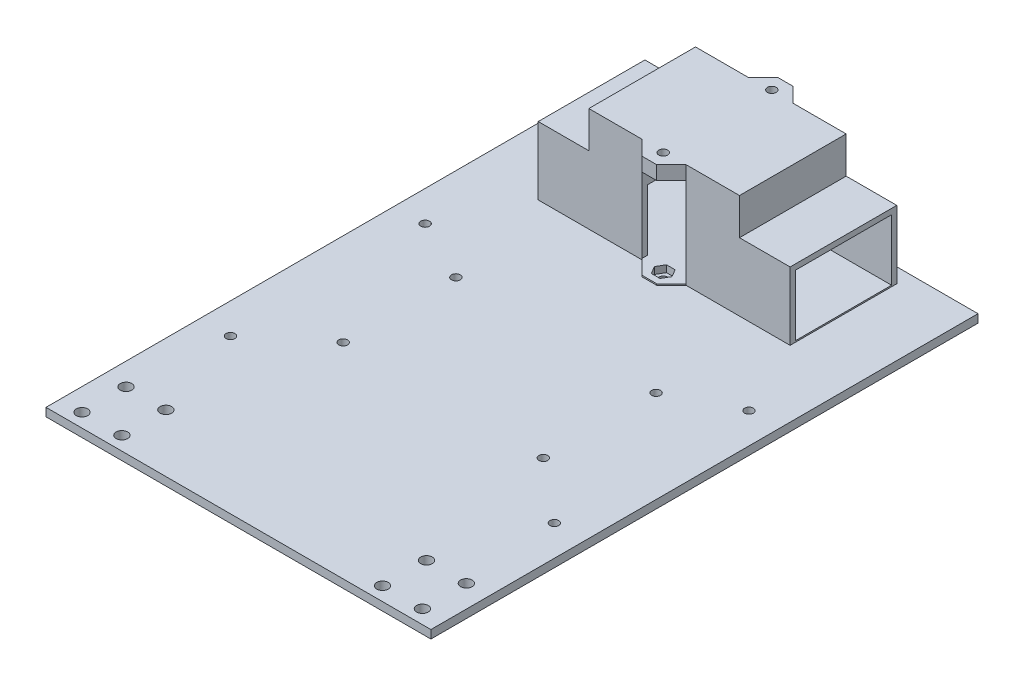
SolidWorks part; units mm, degrees
ref_plane "Front Plane" through (0, 0, 0) normal (0, 0, 1) x (1, 0, 0)
ref_plane "Top Plane" through (0, 0, 0) normal (0, 1, 0) x (1, 0, 0)
ref_plane "Right Plane" through (0, 0, 0) normal (1, 0, 0) x (0, 0, -1)
sketch "Sketch1" plane through (0, 0, 0) normal (0, 1, 0) x (1, 0, 0)
  line L5 (-70, -99) -> (70, -99)
  line L6 (-70, -99) -> (-70, 99)
  line L7 (-70, 99) -> (70, 99)
  line L8 (70, -99) -> (70, 99)
  line L9 (-70, -99) -> (70, 99) construction
  line L10 (-70, 99) -> (70, -99) construction
  point P0 (0, 0)
extrude "Boss-Extrude1" add sketch "Sketch1" along normal blind 3
sketch "Sketch2" plane through (0, 3, 0) normal (0, 1, 0) x (1, 0, 0)
  circle A1 centre (-47.4, -94) radius 2.1
  circle A2 centre (47.4, -94) radius 2.1
  circle A3 centre (-61.9, -94) radius 2.1
  circle A5 centre (61.9, -94) radius 2.1
  circle A6 centre (-47.4, -78) radius 2.1
  circle A7 centre (-61.9, -78) radius 2.1
  circle A8 centre (61.9, -78) radius 2.1
  circle A9 centre (47.4, -78) radius 2.1
extrude "Cut-Extrude1" cut sketch "Sketch2" against normal blind 3
sketch "Sketch3" plane through (0, 3, 0) normal (0, 1, 0) x (1, 0, 0)
  circle A0 centre (-58.9, 27.8) radius 1.6
  circle A1 centre (-58.9, -43) radius 1.6
  circle A2 centre (58.9, -43) radius 1.6
  circle A3 centre (58.9, 27.8) radius 1.6
extrude "Cut-Extrude2" cut sketch "Sketch3" against normal blind 3
sketch "Sketch4" plane through (0, 0, -99) normal (0, 0, -1) x (-1, 0, 0)
  line L4 (-70, 0) -> (70, 0)
  line L5 (70, 0) -> (70, 3)
  line L6 (70, 3) -> (-70, 3)
  line L7 (-70, 3) -> (-70, 0)
  line L8 (-70, 0) -> (70, 0)
  line L9 (70, 0) -> (70, 3)
  line L10 (70, 3) -> (-70, 3)
  line L11 (-70, 3) -> (-70, 0)
  dimension "D1" = 0
extrude "Boss-Extrude2" add sketch "Sketch4" along normal blind 1
sketch "Sketch5" plane through (0, 3, 0) normal (0, 1, 0) x (1, 0, 0)
  circle A0 centre (0, 95) radius 1.6
  circle A1 centre (0, 55.5) radius 1.6
extrude "Cut-Extrude3" cut sketch "Sketch5" against normal blind 16
sketch "Sketch6" plane through (0, 3, 0) normal (0, 1, 0) x (1, 0, 0)
  line L0 (-45.8069, 94.65) -> (-8, 94.65)
  line L1 (-43.8069, 92.65) -> (-8, 92.65)
  line L2 (-43.8069, 57.85) -> (-8, 57.85)
  line L3 (-44, 92.65) -> (-8, 92.65)
  line L4 (-43.8069, 92.65) -> (-43.8069, 57.85)
  line L5 (43.8069, 92.65) -> (43.8069, 57.85)
  line L6 (45.8069, 94.65) -> (45.8069, 55.85)
  line L7 (-45.8069, 55.85) -> (-8, 55.85)
  line L8 (-45.8069, 94.65) -> (-45.8069, 55.85)
  line L9 (8, 94.65) -> (45.8069, 94.65)
  line L14 (8, 55.85) -> (45.8069, 55.85)
  line L15 (8, 57.85) -> (43.8069, 57.85)
  line L20 (-8, 94.65) -> (-8, 92.65)
  line L21 (8, 94.65) -> (8, 92.65)
  line L22 (-45.8069, 94.65) -> (45.8069, 94.65) construction
  line L23 (8, 92.65) -> (43.8069, 92.65)
  line L24 (-43.8069, 92.65) -> (43.8069, 92.65) construction
  line L25 (8, 92.65) -> (44, 92.65)
  line L26 (-45.8069, 55.85) -> (45.8069, 55.85) construction
  line L27 (-43.8069, 57.85) -> (43.8069, 57.85) construction
  line L28 (-8, 57.85) -> (-8, 55.85)
  line L29 (8, 57.85) -> (8, 55.85)
  dimension "D1" = 2
extrude "Boss-Extrude3" add sketch "Sketch6" along normal blind 21 contours L23 L5 L15 L14 L6 L9 | L1 L4 L2 L28 L7 L8 L0 L20 region at (25.9034, 3, -93.1917)
sketch "Sketch7" plane through (43.8069, 0, 0) normal (-1, 0, 0) x (0, 0, 1)
  line L4 (-92.65, 3) -> (-57.85, 3)
  line L5 (-57.85, 3) -> (-57.85, 24)
  line L6 (-57.85, 24) -> (-92.65, 24)
  line L7 (-92.65, 24) -> (-92.65, 3)
  line L8 (-92.65, 3) -> (-57.85, 3)
  line L9 (-57.85, 3) -> (-57.85, 24)
  line L10 (-57.85, 24) -> (-92.65, 24)
  line L11 (-92.65, 24) -> (-92.65, 3)
  dimension "D1" = 0
extrude "Cut-Extrude4" cut sketch "Sketch7" against normal blind 21
sketch "Sketch9" plane through (0, 24, 0) normal (0, 1, 0) x (1, 0, 0)
  line L1 (-45.8069, 94.65) -> (45.8069, 94.65)
  line L2 (-45.8069, 94.65) -> (-45.8069, 55.85)
  line L3 (-45.8069, 55.85) -> (45.8069, 55.85)
  line L4 (45.8069, 94.65) -> (45.8069, 55.85)
extrude "Boss-Extrude4" add sketch "Sketch9" along normal blind 2
sketch "Sketch12" plane through (-45.8069, 0, 0) normal (-1, 0, 0) x (0, 0, 1)
  line L1 (-94.65, 26) -> (-55.85, 26) construction
  line L4 (-85.25, 3) -> (-65.25, 3)
  line L5 (-85.25, 3) -> (-85.25, 26)
  line L6 (-85.25, 26) -> (-65.25, 26)
  line L7 (-65.25, 3) -> (-65.25, 26)
  line L8 (-85.25, 3) -> (-65.25, 26) construction
  line L9 (-85.25, 26) -> (-65.25, 3) construction
  point P6 (-75.25, 14.5)
extrude "Cut-Extrude8" cut sketch "Sketch12" against normal blind 4
sketch "Sketch13" plane through (-41.8069, 0, 0) normal (-1, 0, 0) x (0, 0, 1)
  line L4 (-65.25, 24) -> (-65.25, 26)
  line L5 (-65.25, 26) -> (-85.25, 26)
  line L6 (-85.25, 26) -> (-85.25, 24)
  line L7 (-85.25, 24) -> (-65.25, 24)
  line L8 (-65.25, 24) -> (-65.25, 26)
  line L9 (-65.25, 26) -> (-85.25, 26)
  line L10 (-85.25, 26) -> (-85.25, 24)
  line L11 (-85.25, 24) -> (-65.25, 24)
  dimension "D1" = 0
extrude "Boss-Extrude5" add sketch "Sketch13" along normal blind 4
sketch "Sketch15" plane through (0, 0, -55.85) normal (0, 0, 1) x (1, 0, 0)
  line L0 (-45.8069, 26) -> (45.8069, 26) construction
  line L1 (-8, 24) -> (8, 24)
  line L2 (-8, 24) -> (-8, 26)
  line L3 (-8, 26) -> (8, 26)
  line L4 (8, 24) -> (8, 26)
extrude "Boss-Extrude6" add sketch "Sketch15" along normal blind 5.35
sketch "Sketch16" plane through (0, 0, -94.65) normal (0, 0, -1) x (-1, 0, 0)
  line L4 (8, 24) -> (8, 26)
  line L5 (-8, 24) -> (8, 24)
  line L6 (-8, 26) -> (-8, 24)
  line L7 (8, 26) -> (-8, 26)
  line L8 (8, 24) -> (8, 26)
  line L9 (-8, 24) -> (8, 24)
  line L10 (-8, 26) -> (-8, 24)
  line L11 (8, 26) -> (-8, 26)
  dimension "D1" = 0
extrude "Boss-Extrude7" add sketch "Sketch16" along normal up to surface (5.35 mm away) up to face at (0, 1.5, -100)
sketch "Sketch17" plane through (0, 26, 0) normal (0, 1, 0) x (1, 0, 0)
  circle A0 centre (0, 55.5) radius 1.6 construction
  circle A1 centre (0, 55.5) radius 1.6
  circle A2 centre (0, 95) radius 1.6 construction
  circle A3 centre (0, 95) radius 1.6
extrude "Cut-Extrude9" cut sketch "Sketch17" against normal blind 6
chamfer "Chamfer1" distance 5.35 angle 45 4 edges at (-8, 25, -50.5) (8, 25, -50.5) (8, 25, -100) (-8, 25, -100)
sketch "Sketch18" plane through (0, 3, 0) normal (0, 1, 0) x (1, 0, 0)
  circle A4 centre (36.4, -24.5) radius 1.6
  circle A5 centre (36.4, 16.5) radius 1.6
  circle A6 centre (-36.4, 16.5) radius 1.6
  circle A7 centre (-36.4, -24.5) radius 1.6
extrude "Cut-Extrude10" cut sketch "Sketch18" against normal blind 6
sketch "Sketch19" plane through (0, 26, 0) normal (0, 1, 0) x (1, 0, 0)
  line L12 (-45.8069, 55.85) -> (-8, 55.85)
  line L13 (-8, 55.85) -> (-2.65, 50.5)
  line L14 (-2.65, 50.5) -> (2.65, 50.5)
  line L15 (2.65, 50.5) -> (8, 55.85)
  line L16 (8, 55.85) -> (45.8069, 55.85)
  line L17 (45.8069, 55.85) -> (45.8069, 94.65)
  line L18 (45.8069, 94.65) -> (8, 94.65)
  line L19 (8, 94.65) -> (2.65, 100)
  line L20 (2.65, 100) -> (-2.65, 100)
  line L21 (-2.65, 100) -> (-8, 94.65)
  line L22 (-8, 94.65) -> (-45.8069, 94.65)
  line L23 (-45.8069, 94.65) -> (-45.8069, 55.85)
  line L24 (-45.8069, 55.85) -> (-8, 55.85)
  line L25 (-8, 55.85) -> (-2.65, 50.5)
  line L26 (-2.65, 50.5) -> (2.65, 50.5)
  line L27 (2.65, 50.5) -> (8, 55.85)
  line L28 (8, 55.85) -> (45.8069, 55.85)
  line L29 (45.8069, 55.85) -> (45.8069, 94.65)
  line L30 (45.8069, 94.65) -> (8, 94.65)
  line L31 (8, 94.65) -> (2.65, 100)
  line L32 (2.65, 100) -> (-2.65, 100)
  line L33 (-2.65, 100) -> (-8, 94.65)
  line L34 (-8, 94.65) -> (-45.8069, 94.65)
  line L35 (-45.8069, 94.65) -> (-45.8069, 55.85)
  circle A0 centre (0, 95) radius 1.6 construction
  circle A1 centre (0, 95) radius 1.6
  circle A2 centre (0, 55.5) radius 1.6 construction
  circle A3 centre (0, 55.5) radius 1.6
  dimension "D1" = 0
extrude "Boss-Extrude8" add sketch "Sketch19" along normal blind 15
sketch "Sketch20" plane through (0, 24, 0) normal (0, -1, 0) x (1, 0, 0)
  line L0 (-8, -55.85) -> (-8, -94.65)
  line L1 (8, -94.65) -> (8, -55.85)
  line L12 (-45.8069, -55.85) -> (-45.8069, -94.65)
  line L13 (-8, -55.85) -> (-45.8069, -55.85)
  line L14 (-2.65, -50.5) -> (-8, -55.85)
  line L15 (2.65, -50.5) -> (-2.65, -50.5)
  line L16 (8, -55.85) -> (2.65, -50.5)
  line L17 (45.8069, -55.85) -> (8, -55.85)
  line L18 (45.8069, -94.65) -> (45.8069, -55.85)
  line L19 (8, -94.65) -> (45.8069, -94.65)
  line L20 (2.65, -100) -> (8, -94.65)
  line L21 (-2.65, -100) -> (2.65, -100)
  line L22 (-8, -94.65) -> (-2.65, -100)
  line L23 (-45.8069, -94.65) -> (-8, -94.65)
  line L26 (-2.65, -50.5) -> (-8, -55.85)
  line L27 (2.65, -50.5) -> (-2.65, -50.5)
  line L28 (8, -55.85) -> (2.65, -50.5)
  line L32 (2.65, -100) -> (8, -94.65)
  line L33 (-2.65, -100) -> (2.65, -100)
  line L34 (-8, -94.65) -> (-2.65, -100)
  dimension "D1" = 0
extrude "Cut-Extrude11" cut sketch "Sketch20" against normal blind 12 body kept at (-8, 3, -94.65)
sketch "Sketch21" plane through (0, 41, 0) normal (0, 1, 0) x (1, 0, 0)
  line L2 (-27.4, 55.85) -> (-27.4, 94.65)
  line L3 (-45.8069, 94.65) -> (-8, 94.65) construction
  line L5 (27.4, 55.85) -> (27.4, 94.65)
  line L6 (8, 94.65) -> (45.8069, 94.65) construction
  line L18 (-45.8069, 94.65) -> (-45.8069, 55.85)
  line L19 (-45.8069, 55.85) -> (-8, 55.85)
  line L20 (-8, 55.85) -> (-2.65, 50.5)
  line L21 (-2.65, 50.5) -> (2.65, 50.5)
  line L22 (2.65, 50.5) -> (8, 55.85)
  line L23 (8, 55.85) -> (45.8069, 55.85)
  line L24 (45.8069, 55.85) -> (45.8069, 94.65)
  line L25 (45.8069, 94.65) -> (8, 94.65)
  line L26 (8, 94.65) -> (2.65, 100)
  line L27 (2.65, 100) -> (-2.65, 100)
  line L28 (-2.65, 100) -> (-8, 94.65)
  line L29 (-8, 94.65) -> (-45.8069, 94.65)
  line L30 (-45.8069, 94.65) -> (-45.8069, 55.85)
  line L31 (-45.8069, 55.85) -> (-27.4, 55.85)
  line L35 (27.4, 55.85) -> (45.8069, 55.85)
  line L36 (45.8069, 55.85) -> (45.8069, 94.65)
  line L37 (45.8069, 94.65) -> (27.4, 94.65)
  line L41 (-27.4, 94.65) -> (-45.8069, 94.65)
  point P10 (-27.4, 75.25)
  point P18 (27.4, 75.25)
  dimension "D1" = 0
extrude "Cut-Extrude12" cut sketch "Sketch21" against normal blind 15
sketch "Sketch22" plane through (0, 24, 0) normal (0, -1, 0) x (1, 0, 0)
  line L4 (45.8069, -57.85) -> (8, -57.85)
  line L5 (8, -57.85) -> (8, -92.65)
  line L6 (8, -92.65) -> (45.8069, -92.65)
  line L7 (45.8069, -92.65) -> (45.8069, -57.85)
  line L8 (45.8069, -57.85) -> (8, -57.85)
  line L9 (8, -57.85) -> (8, -92.65)
  line L10 (8, -92.65) -> (45.8069, -92.65)
  line L11 (45.8069, -92.65) -> (45.8069, -57.85)
  line L16 (-43.8069, -92.65) -> (-8, -92.65)
  line L17 (-8, -92.65) -> (-8, -57.85)
  line L18 (-8, -57.85) -> (-43.8069, -57.85)
  line L19 (-43.8069, -57.85) -> (-43.8069, -65.25)
  line L20 (-43.8069, -65.25) -> (-45.8069, -65.25)
  line L21 (-45.8069, -65.25) -> (-45.8069, -85.25)
  line L22 (-45.8069, -85.25) -> (-43.8069, -85.25)
  line L23 (-43.8069, -85.25) -> (-43.8069, -92.65)
  line L24 (-43.8069, -92.65) -> (-8, -92.65)
  line L25 (-8, -92.65) -> (-8, -57.85)
  line L26 (-8, -57.85) -> (-43.8069, -57.85)
  line L27 (-43.8069, -57.85) -> (-43.8069, -65.25)
  line L28 (-43.8069, -65.25) -> (-45.8069, -65.25)
  line L29 (-45.8069, -65.25) -> (-45.8069, -85.25)
  line L30 (-45.8069, -85.25) -> (-43.8069, -85.25)
  line L31 (-43.8069, -85.25) -> (-43.8069, -92.65)
  dimension "D1" = 0
  dimension "D2" = 0
extrude "Cut-Extrude13" cut sketch "Sketch22" against normal blind 1
sketch "Sketch23" plane through (0, 26, 0) normal (0, 1, 0) x (1, 0, 0)
  line L4 (45.8069, 94.65) -> (27.4, 94.65)
  line L5 (27.4, 94.65) -> (27.4, 55.85)
  line L6 (27.4, 55.85) -> (45.8069, 55.85)
  line L7 (45.8069, 55.85) -> (45.8069, 94.65)
  line L8 (45.8069, 94.65) -> (27.4, 94.65)
  line L9 (27.4, 94.65) -> (27.4, 55.85)
  line L10 (27.4, 55.85) -> (45.8069, 55.85)
  line L11 (45.8069, 55.85) -> (45.8069, 94.65)
  line L12 (-27.4, 94.65) -> (-45.8069, 94.65)
  line L13 (-45.8069, 94.65) -> (-45.8069, 55.85)
  line L14 (-45.8069, 55.85) -> (-27.4, 55.85)
  line L15 (-27.4, 55.85) -> (-27.4, 94.65)
  line L16 (-27.4, 94.65) -> (-45.8069, 94.65)
  line L17 (-45.8069, 94.65) -> (-45.8069, 55.85)
  line L18 (-45.8069, 55.85) -> (-27.4, 55.85)
  line L19 (-27.4, 55.85) -> (-27.4, 94.65)
  dimension "D1" = 0
  dimension "D2" = 0
extrude "Boss-Extrude9" add sketch "Sketch23" along normal blind 1
sketch "Sketch24" plane through (0, 0, -57.85) normal (0, 0, -1) x (-1, 0, 0)
  line L4 (-45.8069, 3) -> (-8, 3)
  line L5 (-8, 3) -> (-8, 25)
  line L6 (-8, 25) -> (-45.8069, 25)
  line L7 (-45.8069, 25) -> (-45.8069, 3)
  line L8 (-45.8069, 3) -> (-8, 3)
  line L9 (-8, 3) -> (-8, 25)
  line L10 (-8, 25) -> (-45.8069, 25)
  line L11 (-45.8069, 25) -> (-45.8069, 3)
  line L12 (8, 3) -> (43.8069, 3)
  line L13 (43.8069, 3) -> (43.8069, 25)
  line L14 (43.8069, 25) -> (8, 25)
  line L15 (8, 25) -> (8, 3)
  line L16 (8, 3) -> (43.8069, 3)
  line L17 (43.8069, 3) -> (43.8069, 25)
  line L18 (43.8069, 25) -> (8, 25)
  line L19 (8, 25) -> (8, 3)
  dimension "D1" = 0
  dimension "D2" = 0
extrude "Cut-Extrude14" cut sketch "Sketch24" against normal blind 0.1
sketch "Sketch25" plane through (0, 0, -92.65) normal (0, 0, 1) x (1, 0, 0)
  line L4 (8, 3) -> (45.8069, 3)
  line L5 (45.8069, 3) -> (45.8069, 25)
  line L6 (45.8069, 25) -> (8, 25)
  line L7 (8, 25) -> (8, 3)
  line L8 (8, 3) -> (45.8069, 3)
  line L9 (45.8069, 3) -> (45.8069, 25)
  line L10 (45.8069, 25) -> (8, 25)
  line L11 (8, 25) -> (8, 3)
  line L12 (-43.8069, 3) -> (-8, 3)
  line L13 (-8, 3) -> (-8, 25)
  line L14 (-8, 25) -> (-43.8069, 25)
  line L15 (-43.8069, 25) -> (-43.8069, 3)
  line L16 (-43.8069, 3) -> (-8, 3)
  line L17 (-8, 3) -> (-8, 25)
  line L18 (-8, 25) -> (-43.8069, 25)
  line L19 (-43.8069, 25) -> (-43.8069, 3)
  dimension "D1" = 0
  dimension "D2" = 0
extrude "Cut-Extrude15" cut sketch "Sketch25" against normal blind 0.1
sketch "Sketch26" plane through (0, 36, 0) normal (0, -1, 0) x (1, 0, 0)
  line L1 (3.1754, -55.5) -> (1.5877, -52.75)
  line L2 (1.5877, -52.75) -> (-1.5877, -52.75)
  line L3 (-1.5877, -52.75) -> (-3.1754, -55.5)
  line L4 (-3.1754, -55.5) -> (-1.5877, -58.25)
  line L5 (-1.5877, -58.25) -> (1.5877, -58.25)
  line L6 (1.5877, -58.25) -> (3.1754, -55.5)
  line L7 (3.1754, -95) -> (1.5877, -92.25)
  line L8 (1.5877, -92.25) -> (-1.5877, -92.25)
  line L9 (-1.5877, -92.25) -> (-3.1754, -95)
  line L10 (-3.1754, -95) -> (-1.5877, -97.75)
  line L11 (-1.5877, -97.75) -> (1.5877, -97.75)
  line L12 (1.5877, -97.75) -> (3.1754, -95)
  circle A0 centre (0, -55.5) radius 2.75 construction
  circle A1 centre (0, -95) radius 2.75 construction
extrude "Cut-Extrude16" cut sketch "Sketch26" against normal blind 2.6
sketch "Sketch27" plane through (0, 3, 0) normal (0, 1, 0) x (1, 0, 0)
  line L1 (3.1754, 55.5) -> (1.5877, 58.25)
  line L2 (1.5877, 58.25) -> (-1.5877, 58.25)
  line L3 (-1.5877, 58.25) -> (-3.1754, 55.5)
  line L4 (-3.1754, 55.5) -> (-1.5877, 52.75)
  line L5 (-1.5877, 52.75) -> (1.5877, 52.75)
  line L6 (1.5877, 52.75) -> (3.1754, 55.5)
  circle A0 centre (0, 55.5) radius 2.75 construction
extrude "Cut-Extrude17" cut sketch "Sketch27" against normal blind 2
sketch "Sketch28" plane through (0, 25, 0) normal (0, -1, 0) x (1, 0, 0)
  line L4 (45.8069, -92.75) -> (45.8069, -57.75)
  line L5 (45.8069, -57.75) -> (8, -57.75)
  line L6 (8, -57.75) -> (8, -92.75)
  line L7 (8, -92.75) -> (45.8069, -92.75)
  line L8 (-43.8069, -85.25) -> (-43.8069, -92.75)
  line L9 (-43.8069, -92.75) -> (-8, -92.75)
  line L10 (-8, -92.75) -> (-8, -57.75)
  line L11 (-8, -57.75) -> (-43.8069, -57.75)
  line L12 (-43.8069, -57.75) -> (-43.8069, -65.25)
  line L13 (-43.8069, -65.25) -> (-45.8069, -65.25)
  line L14 (-45.8069, -65.25) -> (-45.8069, -85.25)
  line L15 (-45.8069, -85.25) -> (-43.8069, -85.25)
  line L16 (-43.8069, -85.25) -> (-43.8069, -92.75)
  line L17 (-43.8069, -92.75) -> (-8, -92.75)
  line L18 (-8, -92.75) -> (-8, -57.75)
  line L19 (-8, -57.75) -> (-43.8069, -57.75)
  line L20 (-43.8069, -57.75) -> (-43.8069, -65.25)
  line L21 (-43.8069, -65.25) -> (-45.8069, -65.25)
  line L22 (-45.8069, -65.25) -> (-45.8069, -85.25)
  line L23 (-45.8069, -85.25) -> (-43.8069, -85.25)
  line L24 (45.8069, -92.75) -> (45.8069, -57.75)
  line L25 (45.8069, -57.75) -> (8, -57.75)
  line L26 (8, -57.75) -> (8, -92.75)
  line L27 (8, -92.75) -> (45.8069, -92.75)
  dimension "D1" = 0
  dimension "D2" = 0
extrude "Cut-Extrude18" cut sketch "Sketch28" against normal blind 0.5
sketch "Sketch29" plane through (0, 27, 0) normal (0, 1, 0) x (1, 0, 0)
  line L4 (45.8069, 55.85) -> (45.8069, 94.65)
  line L5 (45.8069, 94.65) -> (27.4, 94.65)
  line L6 (27.4, 94.65) -> (27.4, 55.85)
  line L7 (27.4, 55.85) -> (45.8069, 55.85)
  line L8 (45.8069, 55.85) -> (45.8069, 94.65)
  line L9 (45.8069, 94.65) -> (27.4, 94.65)
  line L10 (27.4, 94.65) -> (27.4, 55.85)
  line L11 (27.4, 55.85) -> (45.8069, 55.85)
  line L12 (-27.4, 55.85) -> (-27.4, 94.65)
  line L13 (-27.4, 94.65) -> (-45.8069, 94.65)
  line L14 (-45.8069, 94.65) -> (-45.8069, 55.85)
  line L15 (-45.8069, 55.85) -> (-27.4, 55.85)
  line L16 (-27.4, 55.85) -> (-27.4, 94.65)
  line L17 (-27.4, 94.65) -> (-45.8069, 94.65)
  line L18 (-45.8069, 94.65) -> (-45.8069, 55.85)
  line L19 (-45.8069, 55.85) -> (-27.4, 55.85)
  dimension "D1" = 0
  dimension "D2" = 0
extrude "Cut-Extrude19" cut sketch "Sketch29" against normal blind 0.5
sketch "Sketch30" plane through (0, 3, 0) normal (0, 1, 0) x (1, 0, 0)
  line L4 (45.8069, 92.75) -> (8, 92.75)
  line L5 (45.8069, 57.75) -> (45.8069, 92.75)
  line L6 (8, 57.75) -> (45.8069, 57.75)
  line L7 (8, 92.75) -> (8, 57.75)
  line L8 (45.8069, 92.75) -> (8, 92.75)
  line L9 (45.8069, 57.75) -> (45.8069, 92.75)
  line L10 (8, 57.75) -> (45.8069, 57.75)
  line L11 (8, 92.75) -> (8, 57.75)
  line L16 (-43.8069, 85.25) -> (-45.8069, 85.25)
  line L17 (-43.8069, 92.75) -> (-43.8069, 85.25)
  line L18 (-8, 92.75) -> (-43.8069, 92.75)
  line L19 (-8, 57.75) -> (-8, 92.75)
  line L20 (-43.8069, 57.75) -> (-8, 57.75)
  line L21 (-43.8069, 65.25) -> (-43.8069, 57.75)
  line L22 (-45.8069, 65.25) -> (-43.8069, 65.25)
  line L23 (-45.8069, 85.25) -> (-45.8069, 65.25)
  line L24 (-43.8069, 85.25) -> (-45.8069, 85.25)
  line L25 (-43.8069, 92.75) -> (-43.8069, 85.25)
  line L26 (-8, 92.75) -> (-43.8069, 92.75)
  line L27 (-8, 57.75) -> (-8, 92.75)
  line L28 (-43.8069, 57.75) -> (-8, 57.75)
  line L29 (-43.8069, 65.25) -> (-43.8069, 57.75)
  line L30 (-45.8069, 65.25) -> (-43.8069, 65.25)
  line L31 (-45.8069, 85.25) -> (-45.8069, 65.25)
  dimension "D1" = 0
  dimension "D2" = 0
extrude "Boss-Extrude10" add sketch "Sketch30" along normal blind 0.5
sketch "Sketch31" plane through (0, 3, 0) normal (0, 1, 0) x (1, 0, 0)
  line L6 (1.5877, 52.75) -> (3.1754, 55.5)
  line L7 (3.1754, 55.5) -> (1.5877, 58.25)
  line L8 (1.5877, 58.25) -> (-1.5877, 58.25)
  line L9 (-1.5877, 58.25) -> (-3.1754, 55.5)
  line L10 (-3.1754, 55.5) -> (-1.5877, 52.75)
  line L11 (-1.5877, 52.75) -> (1.5877, 52.75)
  line L12 (-27.4, 94.65) -> (-27.4, 55.85)
  line L13 (-27.4, 55.85) -> (-8, 55.85)
  line L14 (-8, 55.85) -> (-2.65, 50.5)
  line L15 (-2.65, 50.5) -> (2.65, 50.5)
  line L16 (2.65, 50.5) -> (8, 55.85)
  line L17 (8, 55.85) -> (27.4, 55.85)
  line L18 (27.4, 55.85) -> (27.4, 94.65)
  line L19 (27.4, 94.65) -> (8, 94.65)
  line L20 (8, 94.65) -> (2.65, 100)
  line L21 (2.65, 100) -> (-2.65, 100)
  line L22 (-2.65, 100) -> (-8, 94.65)
  line L23 (-8, 94.65) -> (-27.4, 94.65)
  line L24 (-27.4, 94.65) -> (-27.4, 55.85)
  line L25 (-27.4, 55.85) -> (-8, 55.85)
  line L26 (-8, 55.85) -> (-2.65, 50.5)
  line L27 (-2.65, 50.5) -> (2.65, 50.5)
  line L28 (2.65, 50.5) -> (8, 55.85)
  line L29 (8, 55.85) -> (27.4, 55.85)
  line L30 (27.4, 55.85) -> (27.4, 94.65)
  line L31 (27.4, 94.65) -> (8, 94.65)
  line L32 (8, 94.65) -> (2.65, 100)
  line L33 (2.65, 100) -> (-2.65, 100)
  line L34 (-2.65, 100) -> (-8, 94.65)
  line L35 (-8, 94.65) -> (-27.4, 94.65)
  line L36 (1.5877, 52.75) -> (3.1754, 55.5)
  line L37 (3.1754, 55.5) -> (1.5877, 58.25)
  line L38 (1.5877, 58.25) -> (-1.5877, 58.25)
  line L39 (-1.5877, 58.25) -> (-3.1754, 55.5)
  line L40 (-3.1754, 55.5) -> (-1.5877, 52.75)
  line L41 (-1.5877, 52.75) -> (1.5877, 52.75)
  circle A0 centre (0, 95) radius 1.6 construction
  circle A1 centre (0, 95) radius 1.6
  dimension "D1" = 0
  dimension "D2" = 0
extrude "Boss-Extrude11" add sketch "Sketch31" along normal blind 0.5
sketch "Sketch32" plane through (0, 3.5, 0) normal (0, 1, 0) x (1, 0, 0)
  line L1 (3.1754, 95) -> (1.5877, 97.75)
  line L2 (1.5877, 97.75) -> (-1.5877, 97.75)
  line L3 (-1.5877, 97.75) -> (-3.1754, 95)
  line L4 (-3.1754, 95) -> (-1.5877, 92.25)
  line L5 (-1.5877, 92.25) -> (1.5877, 92.25)
  line L6 (1.5877, 92.25) -> (3.1754, 95)
  circle A0 centre (0, 95) radius 2.75 construction
extrude "Cut-Extrude20" cut sketch "Sketch32" against normal blind 2.5
sketch "Sketch33" plane through (0, 25.5, 0) normal (0, -1, 0) x (1, 0, 0)
  line L4 (8, -92.75) -> (45.8069, -92.75)
  line L5 (45.8069, -92.75) -> (45.8069, -57.75)
  line L6 (45.8069, -57.75) -> (8, -57.75)
  line L7 (8, -57.75) -> (8, -92.75)
  line L8 (8, -92.75) -> (45.8069, -92.75)
  line L9 (45.8069, -92.75) -> (45.8069, -57.75)
  line L10 (45.8069, -57.75) -> (8, -57.75)
  line L11 (8, -57.75) -> (8, -92.75)
  line L16 (-45.8069, -85.25) -> (-43.8069, -85.25)
  line L17 (-43.8069, -85.25) -> (-43.8069, -92.75)
  line L18 (-43.8069, -92.75) -> (-8, -92.75)
  line L19 (-8, -92.75) -> (-8, -57.75)
  line L20 (-8, -57.75) -> (-43.8069, -57.75)
  line L21 (-43.8069, -57.75) -> (-43.8069, -65.25)
  line L22 (-43.8069, -65.25) -> (-45.8069, -65.25)
  line L23 (-45.8069, -65.25) -> (-45.8069, -85.25)
  line L24 (-45.8069, -85.25) -> (-43.8069, -85.25)
  line L25 (-43.8069, -85.25) -> (-43.8069, -92.75)
  line L26 (-43.8069, -92.75) -> (-8, -92.75)
  line L27 (-8, -92.75) -> (-8, -57.75)
  line L28 (-8, -57.75) -> (-43.8069, -57.75)
  line L29 (-43.8069, -57.75) -> (-43.8069, -65.25)
  line L30 (-43.8069, -65.25) -> (-45.8069, -65.25)
  line L31 (-45.8069, -65.25) -> (-45.8069, -85.25)
  dimension "D1" = 0
  dimension "D2" = 0
extrude "Cut-Extrude21" cut sketch "Sketch33" against normal blind 0.2
sketch "Sketch34" plane through (0, 3.5, 0) normal (0, 1, 0) x (1, 0, 0)
  line L0 (2.65, 100) -> (8, 100)
  line L2 (-8, 94.65) -> (-8, 100)
  line L3 (-8, 100) -> (-2.65, 100)
  line L4 (8, 94.65) -> (8, 100)
  line L24 (8, 57.75) -> (45.8069, 57.75)
  line L25 (45.8069, 57.75) -> (45.8069, 92.75)
  line L26 (45.8069, 92.75) -> (8, 92.75)
  line L27 (8, 92.75) -> (8, 94.65)
  line L28 (8, 94.65) -> (2.65, 100)
  line L29 (2.65, 100) -> (-2.65, 100)
  line L30 (-2.65, 100) -> (-8, 94.65)
  line L31 (-8, 94.65) -> (-8, 92.75)
  line L32 (-8, 92.75) -> (-43.8069, 92.75)
  line L33 (-43.8069, 92.75) -> (-43.8069, 85.25)
  line L34 (-43.8069, 85.25) -> (-45.8069, 85.25)
  line L35 (-45.8069, 85.25) -> (-45.8069, 65.25)
  line L36 (-45.8069, 65.25) -> (-43.8069, 65.25)
  line L37 (-43.8069, 65.25) -> (-43.8069, 57.75)
  line L38 (-43.8069, 57.75) -> (-8, 57.75)
  line L39 (-8, 57.75) -> (-8, 55.85)
  line L40 (-8, 55.85) -> (-2.65, 50.5)
  line L41 (-2.65, 50.5) -> (2.65, 50.5)
  line L42 (2.65, 50.5) -> (8, 55.85)
  line L43 (8, 55.85) -> (8, 57.75)
  line L48 (8, 94.65) -> (2.65, 100)
  line L50 (-2.65, 100) -> (-8, 94.65)
  dimension "D1" = 0
extrude "Boss-Extrude12" add sketch "Sketch34" against normal blind 1.3
sketch "Sketch35" plane through (0, 26.5, 0) normal (0, 1, 0) x (1, 0, 0)
  line L4 (27.4, 55.85) -> (45.8069, 55.85)
  line L5 (45.8069, 55.85) -> (45.8069, 94.65)
  line L6 (45.8069, 94.65) -> (27.4, 94.65)
  line L7 (27.4, 94.65) -> (27.4, 55.85)
  line L8 (27.4, 55.85) -> (45.8069, 55.85)
  line L9 (45.8069, 55.85) -> (45.8069, 94.65)
  line L10 (45.8069, 94.65) -> (27.4, 94.65)
  line L11 (27.4, 94.65) -> (27.4, 55.85)
  line L12 (-45.8069, 55.85) -> (-27.4, 55.85)
  line L13 (-27.4, 55.85) -> (-27.4, 94.65)
  line L14 (-27.4, 94.65) -> (-45.8069, 94.65)
  line L15 (-45.8069, 94.65) -> (-45.8069, 55.85)
  line L16 (-45.8069, 55.85) -> (-27.4, 55.85)
  line L17 (-27.4, 55.85) -> (-27.4, 94.65)
  line L18 (-27.4, 94.65) -> (-45.8069, 94.65)
  line L19 (-45.8069, 94.65) -> (-45.8069, 55.85)
  dimension "D1" = 0
  dimension "D2" = 0
extrude "Boss-Extrude13" add sketch "Sketch35" along normal blind 1.2
